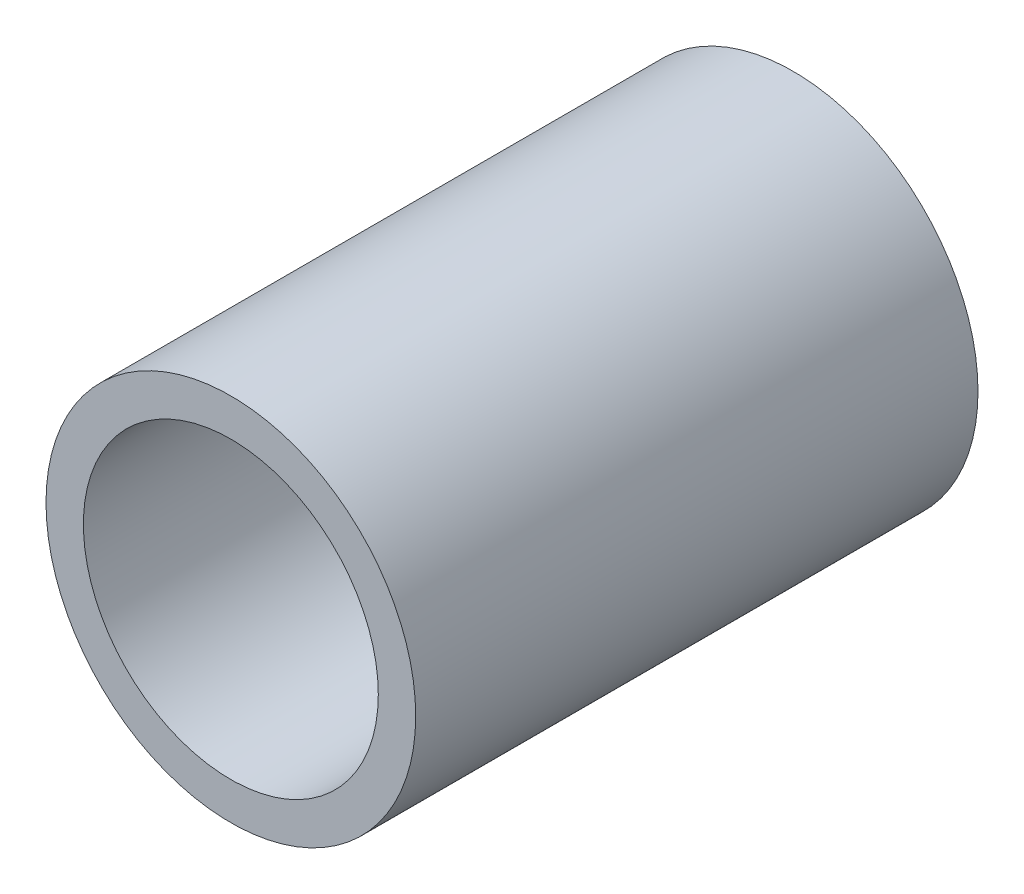
SolidWorks part; units mm, degrees
ref_plane "Front Plane" through (0, 0, 0) normal (0, 0, 1) x (1, 0, 0)
ref_plane "Top Plane" through (0, 0, 0) normal (0, 1, 0) x (1, 0, 0)
ref_plane "Right Plane" through (0, 0, 0) normal (1, 0, 0) x (0, 0, -1)
sketch "Sketch1" plane through (0, 0, 0) normal (0, 0, 1) x (1, 0, 0)
  circle A0 centre (0, 0) radius 16.7005
  dimension "Pipe OD" = 33.401
extrude "Extrude-Thin1" add sketch "Sketch1" along normal mid plane 50.8 thin thin type one direction reverse wall 3.3782
